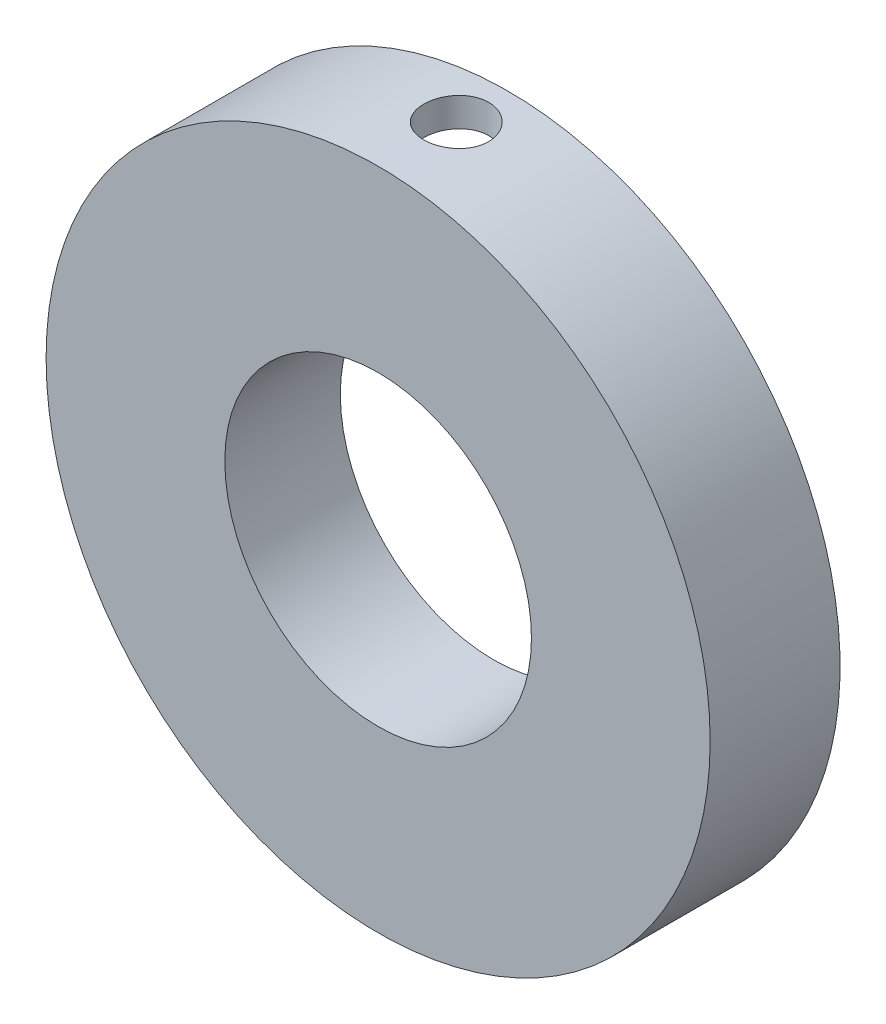
SolidWorks part; units mm, degrees
ref_plane "Front Plane" through (0, 0, 0) normal (0, 0, 1) x (1, 0, 0)
ref_plane "Top Plane" through (0, 0, 0) normal (0, 1, 0) x (1, 0, 0)
ref_plane "Right Plane" through (0, 0, 0) normal (1, 0, 0) x (0, 0, -1)
sketch "Sketch1" plane through (0, 0, 0) normal (0, 0, 1) x (1, 0, 0)
  circle A0 centre (0, 0) radius 10.62
  circle A1 centre (0, 0) radius 23
  dimension "D1" = 21.24
extrude "Boss-Extrude1" add sketch "Sketch1" along normal blind 3
sketch "Sketch2" plane through (0, 0, 3) normal (0, 0, 1) x (1, 0, 0)
  circle A0 centre (0, 0) radius 13
  circle A1 centre (0, 0) radius 10.62
extrude "Boss-Extrude3" add sketch "Sketch2" against normal blind 8
sketch "Sketch3" plane through (0, 0, 0) normal (0, 0, -1) x (-1, 0, 0)
  circle A2 centre (0, 0) radius 23
  circle A3 centre (0, 0) radius 21
extrude "Boss-Extrude4" add sketch "Sketch3" along normal blind 6
ref_plane "Plane1" through (0, 24.9189, 0) normal (0, 1, 0) x (1, 0, 0)
sketch "Sketch4" plane through (0, 24.9189, 0) normal (0, 1, 0) x (1, 0, 0)
  circle A0 centre (0, 2.4072) radius 1.25
  circle A1 centre (0, 2.4072) radius 2.25
  dimension "D1" = 2.5
  dimension "D2" = 4.5
extrude "Cut-Extrude1" cut sketch "Sketch4" against normal blind 17 contours A0
extrude "Cut-Extrude2" cut sketch "Sketch4<3>" against normal blind 7 contours A1
sketch "Sketch4<3>" plane through (0, 24.9189, 0) normal (0, 1, 0) x (1, 0, 0) same geometry as "Sketch4"
